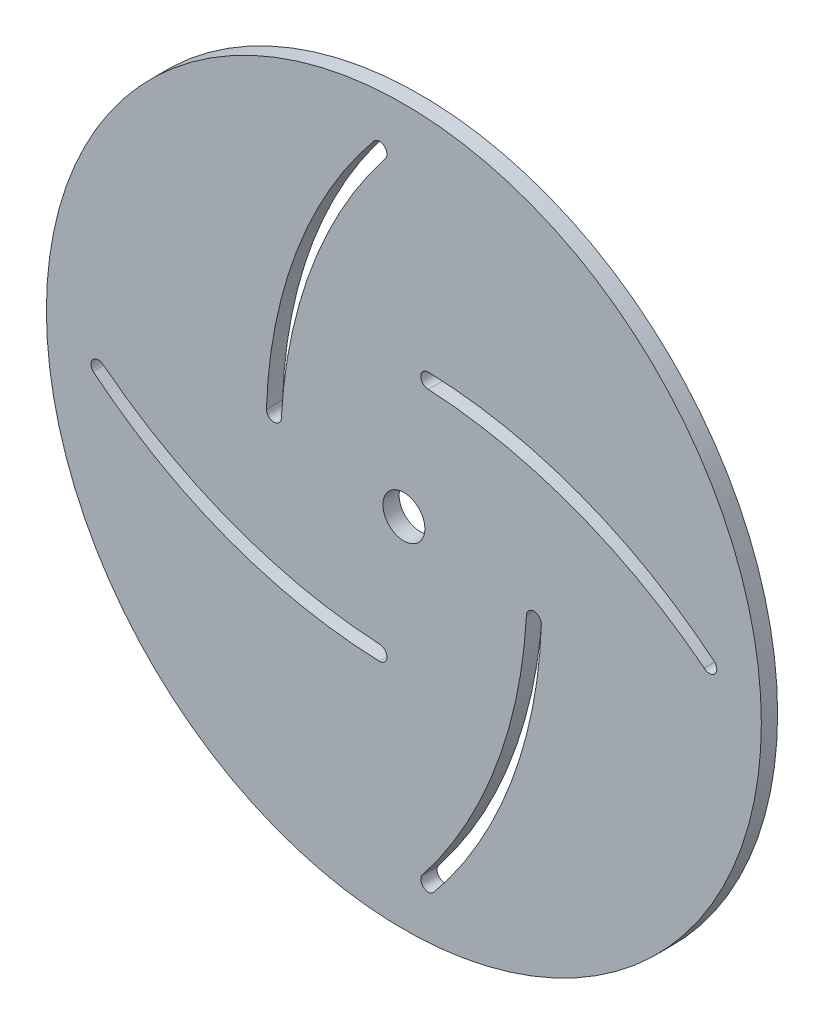
SolidWorks part; units mm, degrees
ref_plane "Front Plane" through (0, 0, 0) normal (0, 0, 1) x (1, 0, 0)
ref_plane "Top Plane" through (0, 0, 0) normal (0, 1, 0) x (1, 0, 0)
ref_plane "Right Plane" through (0, 0, 0) normal (1, 0, 0) x (0, 0, -1)
sketch "Sketch1" plane through (0, 0, 0) normal (0, 0, 1) x (1, 0, 0)
  line L0 (0, 0) -> (0, 69.85) construction
  line L1 (0, 69.85) -> (23.1636, 62.7607) construction
  line L2 (0, 0) -> (-69.85, 0) construction
  line L3 (-4.7625, 59.69) -> (-5.7884, 60.7159) construction
  line L4 (-4.7625, 59.69) -> (-3.7366, 58.6641) construction
  circle A13 centre (0, 0) radius 69.85
  circle A14 centre (0, 0) radius 4.1
  arc A42 (60.7159, 5.7884) -> (4.7776, 26.8568) centre (1.726, -66.0401) ccw
  arc A43 (4.7776, 26.8568) -> (4.7625, 23.943) centre (4.7625, 25.3999) ccw
  arc A44 (4.7625, 23.943) -> (58.6641, 3.7366) centre (-0.38, -71.7708) cw
  arc A46 (60.7159, 5.7884) -> (58.6641, 3.7366) centre (59.69, 4.7625) cw
  arc A47 (-23.943, 4.7625) -> (-3.7366, 58.6641) centre (71.7708, -0.38) cw
  arc A48 (-5.7884, 60.7159) -> (-26.8568, 4.7776) centre (66.0401, 1.726) ccw
  arc A50 (-26.8568, 4.7776) -> (-23.943, 4.7625) centre (-25.3999, 4.7625) ccw
  arc A51 (-5.7884, 60.7159) -> (-3.7366, 58.6641) centre (-4.7625, 59.69) cw
  arc A52 (5.7884, -60.7159) -> (26.8568, -4.7776) centre (-66.0401, -1.726) ccw
  arc A53 (26.8568, -4.7776) -> (23.943, -4.7625) centre (25.3999, -4.7625) ccw
  arc A54 (23.943, -4.7625) -> (3.7366, -58.6641) centre (-71.7708, 0.38) cw
  arc A55 (5.7884, -60.7159) -> (3.7366, -58.6641) centre (4.7625, -59.69) cw
  arc A56 (-60.7159, -5.7884) -> (-4.7776, -26.8568) centre (-1.726, 66.0401) ccw
  arc A57 (-4.7776, -26.8568) -> (-4.7625, -23.943) centre (-4.7625, -25.3999) ccw
  arc A58 (-4.7625, -23.943) -> (-58.6641, -3.7366) centre (0.38, 71.7708) cw
  arc A59 (-60.7159, -5.7884) -> (-58.6641, -3.7366) centre (-59.69, -4.7625) cw
  point P43 (0, 0)
  dimension "D1" = 59.69
  dimension "D2" = 4.7625
  dimension "D3" = 4
extrude "Boss-Extrude1" add sketch "Sketch1" along normal blind 3.175
sketch "Sketch2" plane through (0, 0, 3.175) normal (0, 0, 1) x (1, 0, 0)
  arc A0 (-25.3999, 4.7625) -> (-4.7625, 59.69) centre (66.5458, 1.5573) cw
  point P3 (-140.2437, -28.1794)
sketch "Sketch3" plane through (0, 0, 3.175) normal (0, 0, 1) x (1, 0, 0)
  line L0 (-30.1624, 4.7625) -> (-65.0875, 4.7625)
  line L1 (4.7625, 30.1624) -> (4.7625, 65.0875)
  line L2 (30.1624, -4.7625) -> (65.0875, -4.7625)
  line L3 (-4.7625, -30.1624) -> (-4.7625, -65.0875)
  arc A1 (-65.0875, 4.7625) -> (-9.525, 65.0875) centre (0.5141, 0.0905) cw
  arc A2 (-30.1624, 4.7625) -> (-9.525, 65.0875) centre (45.0213, 12.7344) cw
  arc A3 (4.7625, 30.1624) -> (65.0875, 9.525) centre (12.7344, -45.0213) cw
  arc A4 (4.7625, 65.0875) -> (65.0875, 9.525) centre (0.0905, -0.5141) cw
  arc A5 (30.1624, -4.7625) -> (9.525, -65.0875) centre (-45.0213, -12.7344) cw
  arc A6 (65.0875, -4.7625) -> (9.525, -65.0875) centre (-0.5141, -0.0905) cw
  arc A7 (-4.7625, -30.1624) -> (-65.0875, -9.525) centre (-12.7344, 45.0213) cw
  arc A8 (-4.7625, -65.0875) -> (-65.0875, -9.525) centre (-0.0905, 0.5141) cw
  point P26 (0, 0)
  dimension "D2" = 4.7625
  dimension "D3" = 4
  dimension "D1" = 4.7625
  dimension "D4" = 4.7625
  dimension "D5" = 4.7625
equation "\"D\"= 6in"
